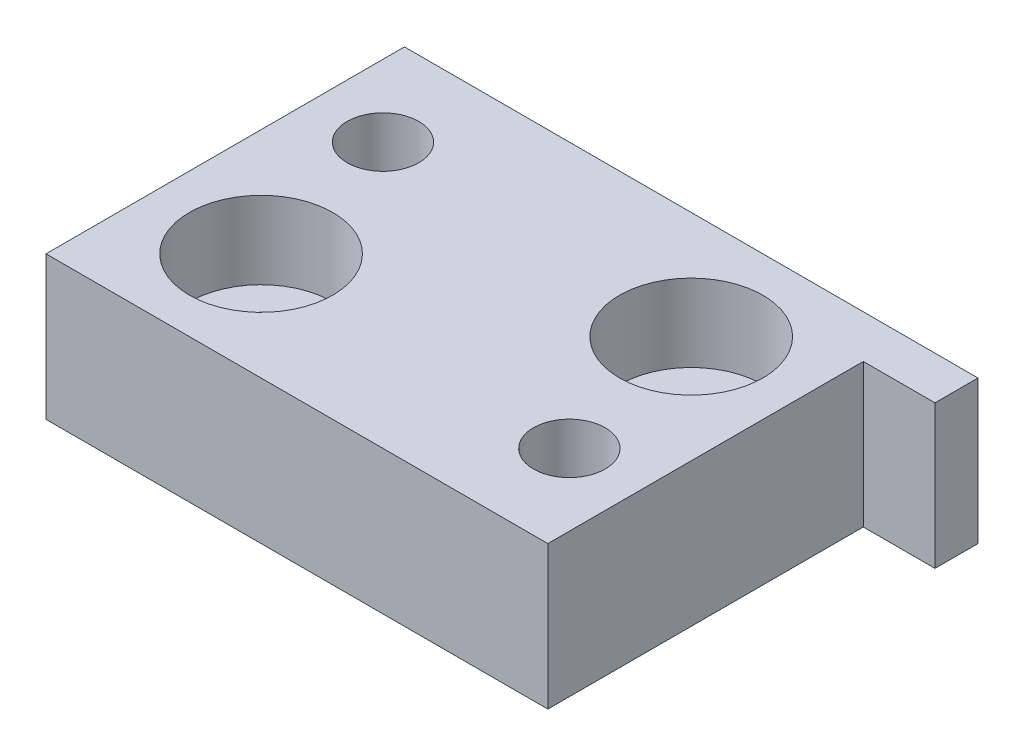
SolidWorks part; units mm, degrees
material "Plain Carbon Steel"
ref_plane "Front Plane" through (0, 0, 0) normal (0, 0, 1) x (1, 0, 0)
ref_plane "Top Plane" through (0, 0, 0) normal (0, 1, 0) x (1, 0, 0)
ref_plane "Right Plane" through (0, 0, 0) normal (1, 0, 0) x (0, 0, -1)
sketch "Sketch1" plane through (0, 0, 0) normal (0, 1, 0) x (1, 0, 0)
  line L1 (-20, -12.5) -> (20, -12.5)
  line L2 (-20, -12.5) -> (-20, 12.5)
  line L3 (-20, 12.5) -> (20, 12.5)
  line L4 (20, -12.5) -> (20, 12.5)
  line L5 (-20, -12.5) -> (20, 12.5) construction
  line L6 (-20, 12.5) -> (20, -12.5) construction
  point P0 (0, 0)
  dimension "D1" = 40
  dimension "D2" = 25
extrude "Boss-Extrude1" add sketch "Sketch1" along normal blind 10
sketch "Sketch3" plane through (0, 10, 0) normal (0, 1, 0) x (1, 0, 0)
  line L0 (20, 12.5) -> (-20, 12.5) construction
  line L1 (20, -12.5) -> (15, -12.5)
  line L2 (20, -12.5) -> (20, 9.5)
  line L3 (20, 9.5) -> (15, 9.5)
  line L4 (15, -12.5) -> (15, 9.5)
  dimension "D1" = 5
  dimension "D2" = 3
extrude "Cut-Extrude2" cut sketch "Sketch3" against normal up to next
hole_wizard "Ø5.0mm Dowel Hole1" positions "Sketch9" profile "Sketch5" hole size "Ø5.0" standard "ISO" end condition through all
sketch "Sketch9" plane through (0, 10, 0) normal (0, 1, 0) x (1, 0, 0)
  line L4 (-2.5, -12.5) -> (-2.5, 12.5) construction
  line L5 (-20, -12.5) -> (15, -12.5) construction
  line L6 (20, 12.5) -> (-20, 12.5) construction
  line L7 (-20, 0) -> (15, 0) construction
  line L8 (-20, 12.5) -> (-20, -12.5) construction
  line L9 (15, 9.5) -> (15, -12.5) construction
  point P31 (10, -6)
  point P33 (-15, 6)
  point P46 (0, 0)
  point P47 (0, 0)
  dimension "D1" = 25
  dimension "D2" = 12
  dimension "D3" = 6
  dimension "D4" = 12.5
sketch "Sketch5" plane through (-15, 10, -6) normal (1, 0, 0) x (0, 0, 1)
  line L0 (0, 0) -> (0, 10)
  line L1 (0, 10) -> (2.5, 10)
  line L2 (2.5, 10) -> (2.5, 0)
  line L5 (2.5, 0) -> (0, 0)
  line L11 (0, -6.35) -> (0, 107.95) construction
  dimension "Thru Hole Dia." = 5
  dimension "Thru Hole Depth" = 10
hole_wizard "CBORE for M5 Hex Socket Head Cap Screw1" positions "Sketch14" profile "Sketch11" counterbore size "M5" standard "ISO" end condition through all
sketch "Sketch14" plane through (0, 10, 0) normal (0, 1, 0) x (1, 0, 0)
  line L0 (-20, 0) -> (15, 0) construction
  line L1 (-20, 12.5) -> (-20, -12.5) construction
  line L2 (15, 9.5) -> (15, -12.5) construction
  line L4 (-2.5, -12.5) -> (-2.5, 12.5) construction
  line L5 (-20, -12.5) -> (15, -12.5) construction
  line L6 (100, 12.5) -> (-20, 12.5) construction
  point P0 (-12.5, -5)
  point P2 (7.5, 5)
  dimension "D1" = 10
  dimension "D2" = 5
  dimension "D3" = 20
  dimension "D4" = 10
sketch "Sketch11" plane through (-12.5, 10, 5) normal (1, 0, 0) x (0, 0, 1)
  line L0 (0, 0) -> (0, 10)
  line L1 (0, 10) -> (2.65, 10)
  line L3 (2.65, 10) -> (2.65, 5.4)
  line L4 (2.65, 5.4) -> (5, 5.4)
  line L5 (5, 5.4) -> (5, 0)
  line L7 (5, 0) -> (0, 0)
  line L11 (0, -6.35) -> (0, 107.95) construction
  dimension "Thru Hole Dia." = 5.3
  dimension "Thru Hole Depth" = 10
  dimension "C'Bore Dia." = 10
  dimension "C'Bore Depth" = 5.4
